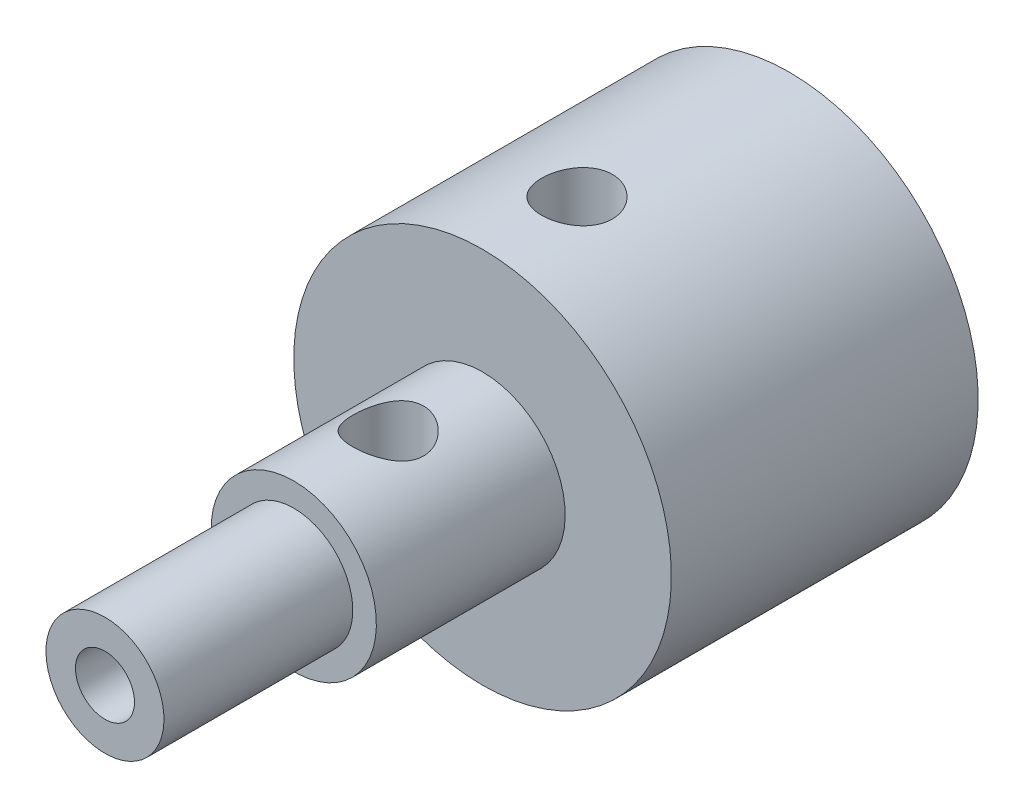
SolidWorks part; units mm, degrees
material "1060 Alloy"
ref_plane "Front Plane" through (0, 0, 0) normal (0, 0, 1) x (1, 0, 0)
ref_plane "Top Plane" through (0, 0, 0) normal (0, 1, 0) x (1, 0, 0)
ref_plane "Right Plane" through (0, 0, 0) normal (1, 0, 0) x (0, 0, -1)
sketch "Sketch1" plane through (0, 0, 0) normal (1, 0, 0) x (0, 0, -1)
  line L0 (0, 0) -> (0, 2.5)
  line L1 (16, 3.5) -> (8, 3.5)
  line L2 (16, 3.5) -> (16, 8)
  line L3 (16.5772, 0) -> (18.5, 3.2)
  line L4 (18.5, 3.2) -> (29, 3.2)
  line L5 (16, 8) -> (29, 8)
  line L6 (29, 3.2) -> (29, 8)
  line L7 (16.5772, 0) -> (0, 0)
  line L8 (8, 3.5) -> (8, 2.5)
  line L9 (8, 2.5) -> (0, 2.5)
  dimension "D1" = 2.5
  dimension "D2" = 8
  dimension "D3" = 3.2
  dimension "D4" = 2.5
  dimension "D5" = 13
  dimension "D6" = 8
  dimension "D7" = 121
  dimension "D8" = 3.5
  dimension "D9" = 8
revolve "Revolve1" add sketch "Sketch1" angle 360 about L7
sketch "Sketch2" plane through (0, 0, 0) normal (0, 1, 0) x (1, 0, 0)
  line L0 (-3.5, 16) -> (3.5, 16) construction
  line L1 (-8, 16) -> (8, 16) construction
  circle A0 centre (0, 20) radius 1.5
  circle A1 centre (0, 12) radius 1.5
  dimension "D2" = 3
  dimension "D3" = 3
  dimension "D1" = 4
  dimension "D4" = 4
extrude "Cut-Extrude1" cut sketch "Sketch2" against normal up to next and the other way up to next
sketch "Sketch4" plane through (0, 0, 0) normal (0, 0, 1) x (1, 0, 0)
  circle A0 centre (0, 0) radius 1.25
  dimension "D1" = 2.5
extrude "Cut-Extrude2" cut sketch "Sketch4" against normal blind 10
